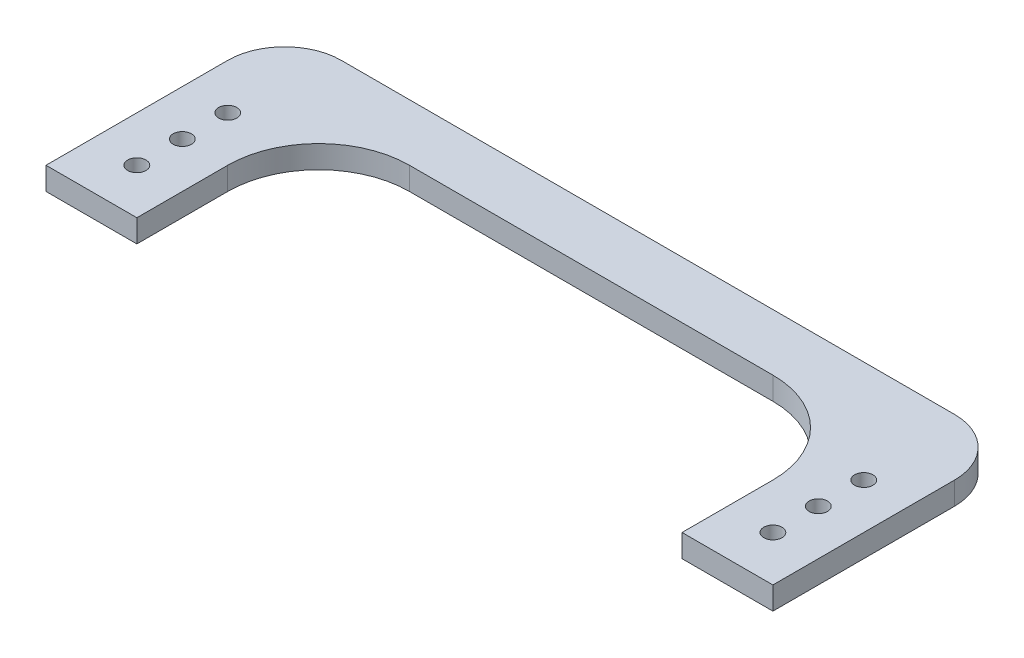
SolidWorks part; units mm, degrees
material "6061-T6 (SS)"
ref_plane "Front" through (0, 0, 0) normal (0, 0, 1) x (1, 0, 0)
ref_plane "Top" through (0, 0, 0) normal (0, 1, 0) x (1, 0, 0)
ref_plane "Right" through (0, 0, 0) normal (1, 0, 0) x (0, 0, -1)
sketch "Sketch1" plane through (0, 0, 0) normal (0, 1, 0) x (1, 0, 0)
  line L0 (-76.2, -25.4) -> (-76.2, 0)
  line L1 (76.2, 0) -> (76.2, -25.4)
  line L2 (76.2, -25.4) -> (101.6, -25.4)
  line L3 (0, 0) -> (0, -66.2098) construction
  line L4 (-76.2, -25.4) -> (-101.6, -25.4)
  line L5 (-101.6, -25.4) -> (-101.6, 25.4)
  line L6 (101.6, 25.4) -> (101.6, -25.4)
  line L8 (-50.8, 25.4) -> (50.8, 25.4)
  line L12 (85.725, 41.275) -> (-85.725, 41.275)
  line L14 (101.6, 6.8059) -> (101.6, -25.4) construction
  line L15 (-101.6, -25.4) -> (-101.6, 6.8059) construction
  arc A6 (60.328, 9.9217) -> (76.2, 0) centre (55.7476, -15.0619) cw construction
  arc A7 (-101.6, 6.8059) -> (-66.4783, 53.4004) centre (82.4959, -95.4263) cw construction
  arc A8 (-66.4783, 53.4004) -> (64.9083, 34.9053) centre (-223.6524, -1539.0619) cw construction
  arc A9 (64.9083, 34.9053) -> (101.6, 6.8059) centre (55.7476, -15.0619) cw construction
  arc A10 (-76.2, 0) -> (-56.5696, 26.8494) centre (82.4959, -95.4263) cw construction
  arc A11 (-56.5696, 26.8494) -> (60.328, 9.9217) centre (-223.6524, -1539.0619) cw construction
  arc A13 (101.6, 25.4) -> (85.725, 41.275) centre (85.725, 25.4) ccw
  arc A15 (-85.725, 41.275) -> (-101.6, 25.4) centre (-85.725, 25.4) ccw
  arc A16 (50.8, 25.4) -> (76.2, 0) centre (50.8, 0) cw
  arc A17 (-76.2, 0) -> (-50.8, 25.4) centre (-50.8, 0) cw
  dimension "D9" = 25.4
  dimension "D1" = 152.4
  dimension "D2" = 50.8
  dimension "D6" = 15.875
  dimension "D3" = 25.4
extrude "Boss-Extrude1" add sketch "Sketch1" along normal blind 6.35
hole_wizard "#10 Clearance Hole1" positions "Sketch2" profile "Sketch3" hole size "#10" standard "ANSI Inch" end condition through all
sketch "Sketch2" plane through (0, 6.35, 0) normal (0, 1, 0) x (1, 0, 0)
  line L3 (-101.6, -25.4) -> (-88.9, -12.7) construction
  line L4 (-88.9, -12.7) -> (-88.9, 0) construction
  line L5 (-88.9, 0) -> (-88.9, 12.7) construction
  line L6 (-88.9, 12.7) -> (-76.2, 25.4) construction
  line L8 (0, 0) -> (0, -50.8) construction
  line L9 (-76.2, -25.4) -> (-76.2, 0) construction
  line L10 (-50.8, 25.4) -> (50.8, 25.4) construction
  point P0 (-88.9, -12.7)
  point P2 (-88.9, 0)
  point P4 (-88.9, 12.7)
  point P29 (88.9, 12.7)
  point P30 (88.9, 0)
  point P31 (88.9, -12.7)
  dimension "D1" = 12.7
sketch "Sketch3" plane through (-88.9, 6.35, 12.7) normal (1, 0, 0) x (0, 0, 1)
  line L0 (0, 0) -> (0, 6.35)
  line L1 (0, 6.35) -> (2.5527, 6.35)
  line L2 (2.5527, 6.35) -> (2.5527, 0)
  line L5 (2.5527, 0) -> (0, 0)
  line L11 (0, -6.35) -> (0, 107.95) construction
  dimension "Thru Hole Dia." = 5.1054
  dimension "Thru Hole Depth" = 6.35
